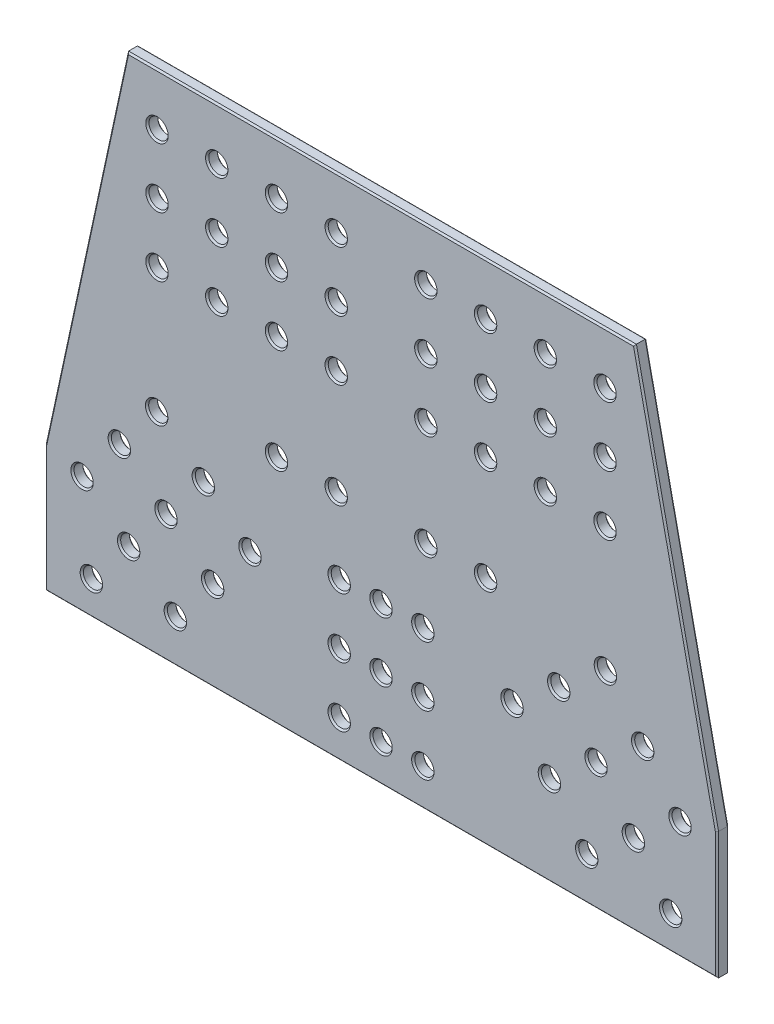
SolidWorks part; units mm, degrees
ref_plane "前视" through (0, 0, 0) normal (0, 0, 1) x (1, 0, 0)
ref_plane "上视" through (0, 0, 0) normal (0, 1, 0) x (1, 0, 0)
ref_plane "右视" through (0, 0, 0) normal (1, 0, 0) x (0, 0, -1)
sketch "草图2" plane through (0, 0, 0) normal (0, 0, 1) x (1, 0, 0)
  line L0 (110, 680) -> (0, 170)
  line L1 (0, 0) -> (900, 0)
  line L2 (0, 0) -> (0, 170)
  line L3 (110, 680) -> (790, 680)
  line L4 (900, 0) -> (900, 170)
  line L5 (450, 732.4608) -> (450, -110.1257) construction
  line L6 (790, 680) -> (900, 170)
  line L7 (110, 610) -> (938.0099, 610) construction
  line L8 (750, 870.5709) -> (750, 471.9627) construction
  line L9 (110, 310) -> (910, 310) construction
  line L10 (110, 530) -> (938.0099, 530) construction
  line L11 (450, 530) -> (944.1948, -87.8821) construction
  line L12 (603.3949, 164.813) -> (806.4775, 327.2426) construction
  line L13 (663.7287, 110.6282) -> (891.7517, 293.0057) construction
  line L14 (711.6834, 46.5423) -> (936.4569, 226.3208) construction
  line L15 (610.0301, 201.8375) -> (761.264, 12.7528) construction
  line L16 (733.9352, 303.0814) -> (876.4232, 124.9314) construction
  line L17 (506, 262.1445) -> (506, 27.5399) construction
  circle A0 centre (450, 50) radius 13
  circle A1 centre (450, 130) radius 13
  circle A2 centre (450, 210) radius 13
  circle A3 centre (837.8826, 45.038) radius 13
  circle A4 centre (62.1174, 45.038) radius 13
  circle A5 centre (506, 210) radius 13
  circle A6 centre (506, 130) radius 13
  circle A7 centre (506, 50) radius 13
  circle A8 centre (394, 50) radius 13
  circle A9 centre (394, 130) radius 13
  circle A10 centre (394, 210) radius 13
  circle A11 centre (510, 310) radius 13
  circle A12 centre (590, 310) radius 13
  circle A13 centre (310, 310) radius 13
  circle A14 centre (390, 310) radius 13
  circle A15 centre (750.4512, 282.4317) radius 13
  circle A16 centre (687.9763, 232.4629) radius 13
  circle A17 centre (800.42, 219.9567) radius 13
  circle A18 centre (850.3888, 157.4818) radius 13
  circle A19 centre (787.9138, 107.513) radius 13
  circle A20 centre (737.945, 169.988) radius 13
  circle A21 centre (725.4388, 57.5442) radius 13
  circle A22 centre (675.4701, 120.0192) radius 13
  circle A23 centre (625.5013, 182.4942) radius 13
  circle A24 centre (274.4987, 182.4942) radius 13
  circle A25 centre (224.5299, 120.0192) radius 13
  circle A26 centre (174.5612, 57.5442) radius 13
  circle A27 centre (162.055, 169.988) radius 13
  circle A28 centre (112.0862, 107.513) radius 13
  circle A29 centre (49.6112, 157.4818) radius 13
  circle A30 centre (99.58, 219.9567) radius 13
  circle A31 centre (212.0237, 232.4629) radius 13
  circle A32 centre (149.5488, 282.4317) radius 13
  point P5 (0, 170)
  point P6 (110, 680)
  point P15 (450, 50)
  dimension "D7" = 50
  dimension "D8" = 26
  dimension "D15" = 26
  dimension "D21" = 26
  dimension "D28" = 26
  dimension "D1" = 900
  dimension "D2" = 680
  dimension "D3" = 170
  dimension "D4" = 110
  dimension "D5" = 70
  dimension "D6" = 40
  dimension "D9" = 80
  dimension "D10" = 80
  dimension "D11" = 80
  dimension "D12" = 56
  dimension "D13" = 80
  dimension "D14" = 300
  dimension "D16" = 60
  dimension "D17" = 80
  dimension "D18" = 80
  dimension "D19" = 38.654
  dimension "D20" = 381
  dimension "D22" = 80
  dimension "D23" = 80
  dimension "D24" = 80
  dimension "D25" = 80
  dimension "D26" = 80
  dimension "D27" = 50
extrude "基体-拉伸" add sketch "草图2" along normal blind 16
sketch "草图3" plane through (0, 0, 16) normal (0, 0, 1) x (1, 0, 0)
  circle A0 centre (750, 610) radius 13
  dimension "D1" = 26
  dimension "D2" = 40
  dimension "D3" = 70
extrude "切除-拉伸1" cut sketch "草图3" against normal through all
pattern_linear "阵列(线性)1" count 4 spacing 80 along (-1, 0, 0) count 3 spacing 80 along (0, -1, 0) of "切除-拉伸1"
pattern_linear "阵列(线性)2" count 2 spacing 360 along (-1, 0, 0) of "阵列(线性)1", "切除-拉伸1"
chamfer "倒角11" distance 2 angle 49 126 edges at (900, 85, 16) (287.4987, 182.4942, 0) (287.4987, 182.4942, 16) (237.5299, 120.0192, 0) (237.5299, 120.0192, 16) (187.5612, 57.5442, 0) (187.5612, 57.5442, 16) (149.055, 169.988, 0) (149.055, 169.988, 16) (99.0862, 107.513, 0) (99.0862, 107.513, 16) (36.6112, 157.4818, 0) (36.6112, 157.4818, 16) (86.58, 219.9567, 0) (86.58, 219.9567, 16) (199.0237, 232.4629, 0) (199.0237, 232.4629, 16) (845, 425, 16) (136.5488, 282.4317, 0) (136.5488, 282.4317, 16) (381, 130, 0) (381, 130, 16) (381, 210, 0) (381, 210, 16) (763, 610, 0) (763, 610, 16) (450, 680, 16) (683, 530, 16) (683, 530, 0) (463, 50, 0) (603, 530, 0) (603, 530, 16) (463, 50, 16) (683, 610, 16) (683, 610, 0) (603, 610, 0) (603, 610, 16) (523, 610, 0) (523, 610, 16) (763, 530, 0) (763, 530, 16) (523, 530, 0) (523, 530, 16) (763, 450, 0) (763, 450, 16) (683, 450, 0) (683, 450, 16) (603, 450, 0) (603, 450, 16) (523, 450, 0) (523, 450, 16) (55, 425, 16) (403, 610, 0) (403, 610, 16) (403, 530, 0) (403, 530, 16) (403, 450, 0) (403, 450, 16) (323, 610, 0) (323, 610, 16) (463, 130, 0) (463, 130, 16) (323, 530, 0) (323, 530, 16) (323, 450, 0) (323, 450, 16) (243, 610, 0) (243, 610, 16) (243, 530, 0) (243, 530, 16) (243, 450, 0) (243, 450, 16) (163, 610, 0) (163, 610, 16) (163, 530, 0) (163, 530, 16) (163, 450, 0) (163, 450, 16) (463, 210, 0) (463, 210, 16) (850.8826, 45.038, 0) (850.8826, 45.038, 16) (49.1174, 45.038, 0) (49.1174, 45.038, 16) (519, 210, 0) (519, 210, 16) (519, 130, 0) (519, 130, 16) (0, 85, 16) (519, 50, 0) (519, 50, 16) (381, 50, 0) (381, 50, 16) (523, 310, 0) (523, 310, 16) (603, 310, 0) (603, 310, 16) (297, 310, 0) (297, 310, 16) (55, 425, 0) (377, 310, 0) (377, 310, 16) (450, 680, 0) (700.9763, 232.4629, 0) (700.9763, 232.4629, 16) (845, 425, 0) (763.4512, 282.4317, 0) (763.4512, 282.4317, 16) (450, 0, 16) (900, 85, 0) (813.42, 219.9567, 0) (813.42, 219.9567, 16) (450, 0, 0) (863.3888, 157.4818, 0) (863.3888, 157.4818, 16) (0, 85, 0) (800.9138, 107.513, 0) (800.9138, 107.513, 16) (750.945, 169.988, 0) (750.945, 169.988, 16) (712.4388, 57.5442, 0) (712.4388, 57.5442, 16) (662.4701, 120.0192, 0) (662.4701, 120.0192, 16) (612.5013, 182.4942, 0) (612.5013, 182.4942, 16)
